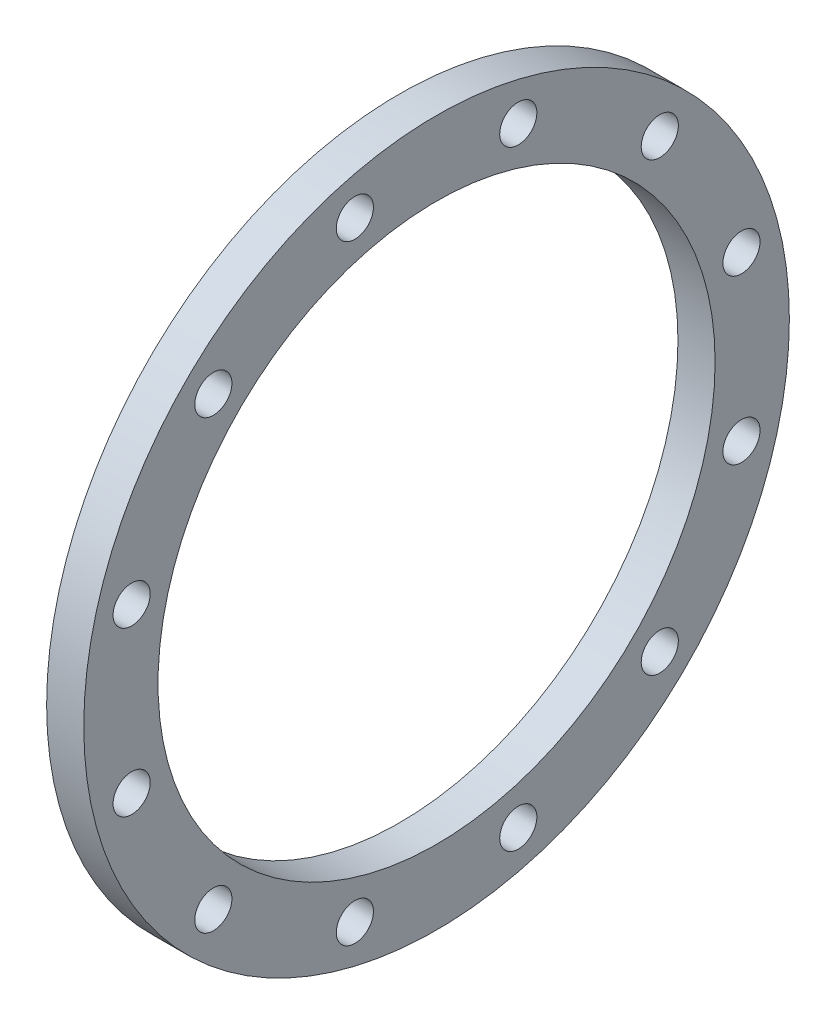
SolidWorks part; units mm, degrees
material "AISI 316 Stainless Steel Sheet (SS)"
ref_plane "Front Plane" through (0, 0, 0) normal (0, 0, 1) x (1, 0, 0)
ref_plane "Top Plane" through (0, 0, 0) normal (0, 1, 0) x (1, 0, 0)
ref_plane "Right Plane" through (0, 0, 0) normal (1, 0, 0) x (0, 0, -1)
other "Center of Mass"
ref_axis "y axis" through (0, 585.7975, 0) along (0, -1, 0)
sketch "Sketch1" plane through (0, 0, 0) normal (0, 1, 0) x (1, 0, 0)
  line L0 (0, -514.3) -> (0, 514.3) construction
  line L5 (-127, -514.3) -> (-127, 514.3)
  line L6 (127, -514.3) -> (127, 514.3)
  line L7 (127, -391.3) -> (-127, -391.3) construction
  line L8 (127, 391.3) -> (-127, 391.3) construction
  arc A0 (-127, -514.3) -> (127, -514.3) centre (0, -514.3) ccw
  arc A1 (127, 514.3) -> (-127, 514.3) centre (0, 514.3) ccw
  point P3 (0, 0)
  point P8 (0, 641.3)
  point P11 (0, -391.3)
  point P14 (0, 391.3)
  point P15 (0, 0)
  point P16 (0, -641.3)
  point P17 (151.9064, -672.3486)
  point P18 (0, -1014.616)
  point P19 (0, -1014.616)
  point P20 (0, -450.9613)
  point P21 (0, -1014.616)
  point P22 (0, -1014.616)
  point P23 (36.2546, -445.4659)
  point P24 (0, -1014.616)
  point P25 (0, 405.6569)
  point P26 (0, 523.2586)
  point P27 (0, 351.6985)
  point P28 (0, 254.8501)
  point P29 (0, 311.5756)
  point P30 (-127, 494.204)
  point P31 (-127, 751.5441)
  point P32 (0, 76.3724)
  point P33 (0, 76.5271)
  point P34 (0, 281.2762)
  point P35 (0, -348.3331)
  dimension "D1" = 250
  dimension "D2" = 250
  dimension "D3" = 254
  dimension "D4" = 391.3
  dimension "D5" = 391.3
sketch "CoM Sketch" plane through (0, 0, 0) normal (1, 0, 0) x (0, 0, -1)
  point P0 (-103.2, 908.41)
  dimension "D1" = 103.2
  dimension "D2" = 908.41
ref_point "CoM"
ref_axis "CoM Axis" through (0, -31.8377, 103.2) along (0, 1, 0)
sketch "Sketch6" plane through (0, 0, 0) normal (1, 0, 0) x (0, 0, -1)
  line L0 (0, 0) -> (0, 316.3) construction
  line L1 (0, 316.3) -> (215.9, 316.3) construction
  circle A0 centre (0, 316.3) radius 190.5
  circle A1 centre (0, 316.3) radius 241.3
  circle A2 centre (0, 316.3) radius 215.9 construction
  circle A3 centre (208.5434, 260.421) radius 12.7
  point P8 (215.9, 278.3052)
  dimension "D1" = 381
  dimension "D2" = 482.6
  dimension "D3" = 431.8
  dimension "D4" = 25.4
  dimension "D6" = 75
  dimension "D5" = 15
extrude "Boss-Extrude1" add sketch "Sketch6" along normal mid plane 25.4 contours A1 | A1 | A0
hole_wizard "7/8 (1) Diameter Hole1" positions "Sketch14" profile "Sketch15" hole size "7/8" standard "ANSI Inch" end condition through all
sketch "Sketch14" plane through (12.7, 0, 0) normal (1, 0, 0) x (0, 0, -1)
  point P0 (208.5434, 260.421)
  point P5 (208.5434, 260.421)
sketch "Sketch15" plane through (12.7, 260.421, -208.5434) normal (0, 1, 0) x (0, 0, -1)
  line L0 (0, 0) -> (0, 25.4)
  line L1 (0, 25.4) -> (12.7, 25.4)
  line L2 (12.7, 25.4) -> (12.7, 0)
  line L5 (12.7, 0) -> (0, 0)
  line L11 (0, -6.35) -> (0, 107.95) construction
  dimension "Thru Hole Dia." = 25.4
  dimension "Thru Hole Depth" = 25.4
pattern_circular "CirPattern1" count 12 over 360 about axis through (12.7, 316.3, 0) along (-1, 0, 0) of "7/8 (1) Diameter Hole1"
sketch "Sketch12" plane through (0, 0, 0) normal (1, 0, 0) x (0, 0, -1)
  line L0 (461.2451, 0) -> (-461.2451, 0) construction
  line L1 (208.9719, 436.95) -> (461.2451, 0) construction
  line L3 (-461.2451, 0) -> (-208.9719, 436.95) construction
  circle A0 centre (0, 316.3) radius 241.3 construction
  point P4 (0, 0)
  dimension "D1" = 60
sketch "Sketch13" plane through (0, 0, 0) normal (1, 0, 0) x (0, 0, -1)
  line L0 (461.2451, 0) -> (-461.2451, 0) construction
  line L1 (461.2451, 0) -> (-461.2451, 0)
  line L2 (461.2451, 0) -> (461.2451, 316.3)
  line L3 (461.2451, 316.3) -> (241.3, 316.3)
  line L4 (0, 316.3) -> (215.9, 316.3) construction
  line L5 (-461.2451, 0) -> (-461.2451, 316.3)
  line L6 (-461.2451, 316.3) -> (-241.3, 316.3)
  circle A0 centre (0, 316.3) radius 241.3 construction
  circle A1 centre (0, 316.3) radius 241.3
sketch "Sketch8" plane through (0, 0, 0) normal (0, 1, 0) x (1, 0, 0)
  line L6 (127, 391.3) -> (-127, 391.3) construction
  line L7 (127, 391.3) -> (-127, 391.3)
sketch "Sketch9" plane through (0, 0, 0) normal (0, 1, 0) x (1, 0, 0)
  line L2 (127, -391.3) -> (-127, -391.3) construction
  line L3 (127, -391.3) -> (-127, -391.3)
sketch "Sketch10" [suppressed] plane through (0, 0, 0) normal (1, 0, 0) x (0, 0, -1)
  line L0 (-370.4518, 316.3) -> (-20.5501, 1192.0785)
  line L1 (-20.5501, 1192.0785) -> (370.4518, 316.3)
  line L2 (-370.4518, 316.3) -> (-370.4518, 1160.538) construction
  line L3 (370.4518, 316.3) -> (370.4518, 1171.0515) construction
  circle A0 centre (370.4518, 316.3) radius 23.8217 construction
  circle A1 centre (-370.4518, 316.3) radius 23.8217 construction
  circle A2 centre (370.4518, 316.3) radius 23.8217
  circle A3 centre (-370.4518, 316.3) radius 23.8217
  point P6 (-20.5501, 1192.0785)
sketch "Bend-Lines1" [suppressed] plane through (0, 0, 0) normal (0, 1, 0) x (1, 0, 0)
sketch "Bounding-Box1" [suppressed] plane through (0, 0, 0) normal (0, 1, 0) x (1, 0, 0)
equation "\"D_flange_hole\"= 1in"
equation "\"h_flange_ring\"= 75mm"
equation "\"w_flange\"= 1in"
equation "\"Di_flange\"= 15in"
equation "\"Dc_flange\"= 17in"
equation "\"Do_flange\"= 19in"
equation "\"h_x_axis\"= \"h_flange_ring\" + ( 1 / 2 ) * \"Do_flange\""
equation "\"standoff_rear\"= 150mm"
equation "\"standoff_front\"= 150mm"
equation "\"D5@Sketch1\"=\"bend_rear\""
equation "\"bend_rear\"= \"Do_flange\" / 2 + \"standoff_rear\""
equation "\"bend_front\"= \"Do_flange\" / 2 + \"standoff_front\""
equation "\"D4@Sketch1\"=\"bend_front\""
equation "\"D6@Sketch6\"=\"h_flange_ring\""
equation "\"D4@Sketch6\"=\"D_flange_hole\""
equation "\"D2@Sketch6\"=\"Do_flange\""
equation "\"D3@Sketch6\"=\"Dc_flange\""
equation "\"D1@Sketch6\"=\"Di_flange\""
equation "\"D1@Boss-Extrude1\"=\"w_flange\""
